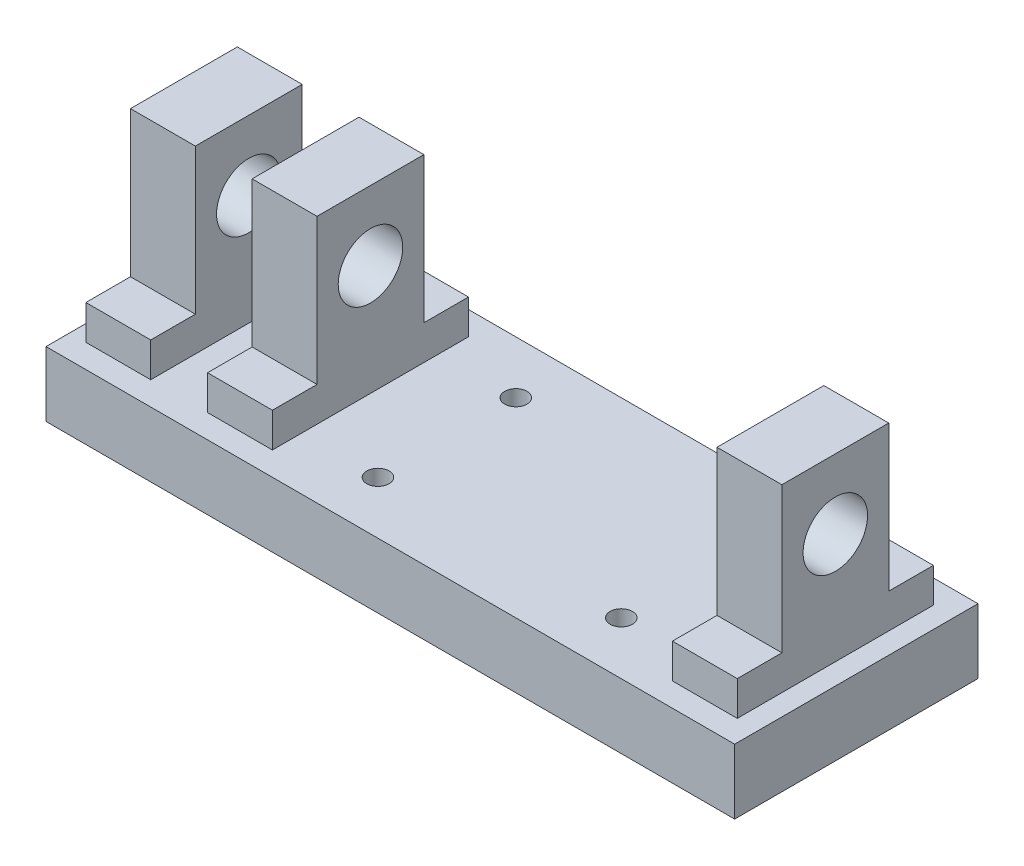
SolidWorks part; units mm, degrees
ref_plane "Front Plane" through (0, 0, 0) normal (0, 0, 1) x (1, 0, 0)
ref_plane "Top Plane" through (0, 0, 0) normal (0, 1, 0) x (1, 0, 0)
ref_plane "Right Plane" through (0, 0, 0) normal (1, 0, 0) x (0, 0, -1)
sketch "Sketch1" plane through (0, 0, 0) normal (0, 1, 0) x (1, 0, 0)
  line L0 (-18.8, -17) -> (46.7, -17) construction
  line L1 (-84.9, -30) -> (84.9, -30)
  line L2 (-84.9, -30) -> (-84.9, 30)
  line L3 (-84.9, 30) -> (84.9, 30)
  line L4 (84.9, -30) -> (84.9, 30)
  line L5 (-84.9, -30) -> (84.9, 30) construction
  line L6 (-84.9, 30) -> (84.9, -30) construction
  line L7 (-16.05, -17) -> (43.95, -17) construction
  line L8 (-16.05, -17) -> (-16.05, 17) construction
  line L9 (-16.05, 17) -> (43.95, 17) construction
  line L10 (43.95, -17) -> (43.95, 17) construction
  line L11 (43.95, 19.75) -> (43.95, -19.75) construction
  line L12 (-16.05, 14.25) -> (-16.05, -14.25) construction
  circle A0 centre (-16.05, -17) radius 2.75
  circle A1 centre (43.95, -17) radius 2.75
  circle A2 centre (43.95, 17) radius 2.75
  circle A3 centre (-16.05, 17) radius 2.75
  point P0 (0, 0)
  point P18 (43.95, 0)
  dimension "D2" = 28.5
  dimension "D1" = 60
  dimension "D3" = 65.5
  dimension "D4" = 39.5
  dimension "D5" = 38.2
  dimension "D6" = 66.1
extrude "Boss-Extrude1" add sketch "Sketch1" along normal blind 16
sketch "Sketch2" plane through (84.9, 0, 0) normal (1, 0, 0) x (0, 0, -1)
  line L0 (-30, 16) -> (30, 16) construction
  line L1 (-24.175, 16) -> (24.175, 16)
  line L2 (-24.175, 16) -> (-24.175, 24.5)
  line L3 (-24.175, 24.5) -> (24.175, 24.5)
  line L4 (24.175, 16) -> (24.175, 24.5)
  line L5 (0, 51.2) -> (0, 60.4) construction
  line L6 (-13.175, 24.5) -> (13.175, 24.5)
  line L7 (-13.175, 24.5) -> (-13.175, 60.4)
  line L8 (-13.175, 60.4) -> (13.175, 60.4)
  line L9 (13.175, 24.5) -> (13.175, 60.4)
  circle A0 centre (0, 43.25) radius 7.95
  point P11 (0, 60.4)
  point P12 (0, 24.5)
  point P13 (0, 16)
  line M13 (30, 16) -> (-30, 16)
  dimension "D4" = 15.9
  dimension "D1" = 44.4
  dimension "D2" = 8.5
  dimension "D3" = 9.2
  dimension "D5" = 48.35
  dimension "D6" = 26.35
extrude "Boss-Extrude2" add sketch "Sketch2" against normal blind 16 from offset 5.18 contours A0 L8 L7 L3 L9 | L4 L3 L2 M13 region at (84.9, 20.25, 0) region at (84.9, 42.45, 12.7297) offset against normal yes
ref_plane "Plane1" through (-80.9, 0, 0) normal (-1, 0, 0) x (0, 0, 1)
extrude "Boss-Extrude3" add sketch "Sketch2<3>" along normal blind 16 from surface contours A0 L8 L7 L3 L9 | L4 L3 L2 M13 region at (84.9, 20.25, 0) region at (84.9, 42.45, 12.7297) starting at plane "Plane1"
sketch "Sketch2<3>" plane through (84.9, 0, 0) normal (1, 0, 0) x (0, 0, -1) same geometry as "Sketch2"
pattern_linear "LPattern1" count 2 spacing 30 along (1, 0, 0) of "Boss-Extrude3"
